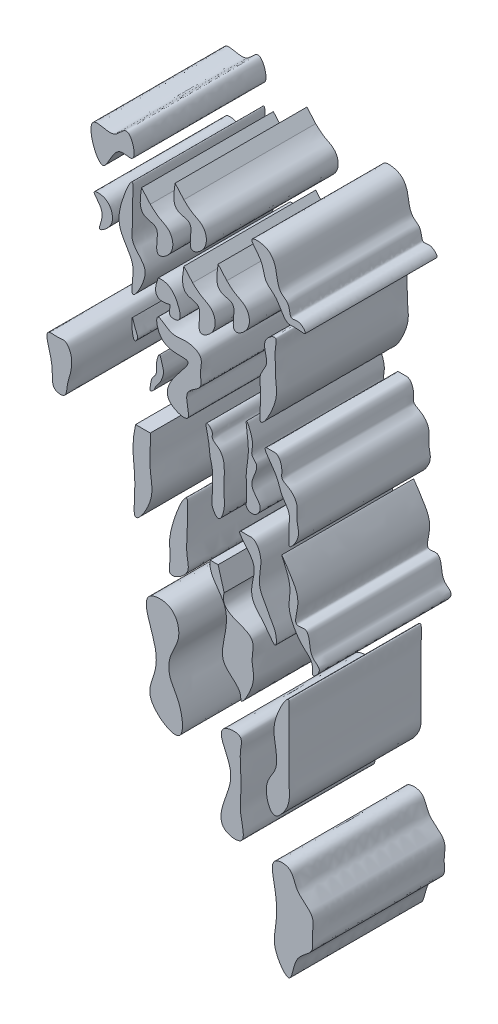
SolidWorks part; units mm, degrees
ref_plane "Front Plane" through (0, 0, 0) normal (0, 0, 1) x (1, 0, 0)
ref_plane "Top Plane" through (0, 0, 0) normal (0, 1, 0) x (1, 0, 0)
ref_plane "Right Plane" through (0, 0, 0) normal (1, 0, 0) x (0, 0, -1)
sketch "Sketch2" plane through (0, 0, 0) normal (0, 0, 1) x (1, 0, 0)
  spline S0 degree 3 poles (-22.2524, -41.5634) (-22.2985, -41.8616) (-22.3666, -42.3025) (-21.7196, -42.3255) (-21.7951, -42.7237) (-21.8014, -43.1952) (-21.2182, -42.8283) (-21.3195, -42.2457) (-21.7452, -42.0964) (-21.9112, -41.9386) (-21.9863, -41.8671) knots 0 0 0 0 0.207427 0.306664 0.423392 0.505521 0.625103 0.799712 0.909285 1 1 1 1
  spline S1 degree 1 poles (-22.2524, -41.5634) (-21.9863, -41.8671) knots 0 0 1 1
  spline S2 degree 3 poles (-19.9285, -42.4109) (-19.9746, -42.7091) (-20.0427, -43.15) (-19.3958, -43.1731) (-19.4713, -43.5712) (-19.4776, -44.0428) (-18.8944, -43.6759) (-18.9956, -43.0932) (-19.4213, -42.9439) (-19.5873, -42.7861) (-19.6625, -42.7146) knots 0 0 0 0 0.207427 0.306664 0.423392 0.505521 0.625103 0.799712 0.909285 1 1 1 1
  spline S3 degree 1 poles (-19.9285, -42.4109) (-19.6625, -42.7146) knots 0 0 1 1
  spline S4 degree 3 poles (-20.9674, -42.985) (-21.0135, -43.2832) (-21.0816, -43.7241) (-20.4347, -43.7472) (-20.5102, -44.1454) (-20.5165, -44.6169) (-19.9333, -44.25) (-20.0345, -43.6674) (-20.4602, -43.518) (-20.6262, -43.3602) (-20.7014, -43.2887) knots 0 0 0 0 0.207427 0.306664 0.423392 0.505521 0.625103 0.799712 0.909285 1 1 1 1
  spline S5 degree 1 poles (-20.9674, -42.985) (-20.7014, -43.2887) knots 0 0 1 1
  spline S6 degree 3 poles (-21.2335, -40.9351) (-21.2796, -41.2333) (-21.3477, -41.6742) (-20.7007, -41.6973) (-20.7762, -42.0954) (-20.7825, -42.567) (-20.1993, -42.2001) (-20.3006, -41.6174) (-20.7263, -41.4681) (-20.8922, -41.3103) (-20.9674, -41.2388) knots 0 0 0 0 0.207427 0.306664 0.423392 0.505521 0.625103 0.799712 0.909285 1 1 1 1
  spline S7 degree 1 poles (-21.2335, -40.9351) (-20.9674, -41.2388) knots 0 0 1 1
  spline S8 degree 3 poles (-23.2714, -42.3458) (-23.8731, -42.3505) (-23.2571, -42.7552) (-23.7014, -43.4714) (-23.1756, -43.0831) (-23.0949, -42.726) (-23.2714, -42.3458) (-23.8731, -42.3505) (-23.2571, -42.7552) knots -0.437374 -0.316138 -0.114431 0 0.189662 0.403883 0.562626 0.683862 0.885569 1 1.189662 1.403883 1.562626 only from (-23.6812, -42.383) to (-23.6812, -42.383)
  spline S9 degree 3 poles (-23.387, -40.5599) (-23.032, -40.6673) (-22.6303, -39.9995) (-22.3217, -41.1038) (-23.1173, -40.7547) (-23.3924, -42.2845) (-24.0158, -40.4835) (-23.387, -40.5599) (-23.032, -40.6673) (-22.6303, -39.9995) knots -0.424588 -0.160212 -0.104486 0 0.110138 0.274978 0.358567 0.575412 0.839788 0.895514 1 1.110138 1.274978 1.358567 only from (-23.0524, -40.5553) to (-23.0524, -40.5553)
  spline S10 degree 3 poles (-22.5598, -42.2755) (-22.4302, -41.158) (-22.9497, -42.3664) (-22.9699, -43.0323) (-22.4602, -43.6249) (-22.5254, -44.0813) (-22.5803, -44.7835) (-22.1406, -44.0125) (-22.1371, -43.4839) (-22.5904, -43.2308) (-22.5129, -42.6878) (-22.5598, -42.2755) (-22.4302, -41.158) (-22.9497, -42.3664) knots -0.24105 -0.196237 -0.113012 0 0.12479 0.252828 0.367116 0.45034 0.495153 0.620686 0.639892 0.75895 0.803763 0.886988 1 1.12479 1.252828 1.367116 only from (-22.5329, -41.5634) to (-22.5329, -41.5634)
  spline S11 degree 3 poles (-21.3311, -45.0368) (-21.8785, -44.491) (-21.7046, -45.5551) (-20.3816, -45.1992) (-21.4324, -46.0924) (-21.5339, -46.8266) (-20.5882, -47.125) (-21.1055, -46.1747) (-20.3669, -45.9979) (-20.5097, -45.5201) (-20.344, -45.0714) (-20.9189, -44.8607) (-21.3311, -45.0368) (-21.8785, -44.491) (-21.7046, -45.5551) knots -0.204826 -0.139309 -0.060255 0 0.079195 0.197262 0.345977 0.419154 0.501786 0.599355 0.681343 0.730128 0.795174 0.860691 0.939745 1 1.079195 1.197262 1.345977 only from (-21.7482, -44.711) to (-21.7482, -44.711)
  spline S12 degree 2 poles (-21.7482, -43.6856) (-22.0062, -44.3801) (-21.391, -44.2015) knots 0 0 0 1 1 1
  spline S13 degree 3 poles (-21.5031, -44.5283) (-21.0997, -44.544) (-21.0716, -44.2973) (-21.17, -43.9986) (-21.3614, -43.6697) (-21.994, -43.6682) (-21.2311, -44.0558) (-21.5031, -44.5283) (-21.0997, -44.544) (-21.0716, -44.2973) knots -0.499676 -0.231732 -0.113108 0 0.067008 0.163276 0.415121 0.500324 0.768268 0.886892 1 1.067008 1.163276 1.415121 only from (-21.1262, -44.4793) to (-21.1262, -44.4793)
  spline S14 degree 3 poles (-18.3873, -41.1949) (-19.1033, -41.1744) (-18.5193, -41.6661) (-18.5663, -42.148) (-18.0752, -42.4207) (-17.9183, -42.9823) (-17.5523, -42.8868) (-17.1653, -42.9863) (-17.4522, -42.6393) (-17.7731, -42.7987) (-17.7388, -42.3751) (-18.1423, -42.1965) (-18.1233, -41.646) (-18.3873, -41.1949) (-19.1033, -41.1744) (-18.5193, -41.6661) knots -0.296451 -0.174734 -0.074505 0 0.090894 0.198006 0.271353 0.397553 0.445449 0.493345 0.547008 0.589582 0.652417 0.703549 0.825266 0.925495 1 1.090894 1.198006 1.271353 only from (-18.8967, -41.2388) to (-18.8967, -41.2388)
  spline S15 degree 3 poles (-18.2274, -43.8795) (-18.1247, -43.3743) (-18.6962, -43.7397) (-18.2963, -44.2516) (-18.6833, -44.6189) (-18.6327, -45.0754) (-18.6345, -45.4055) (-18.7079, -46.233) (-18.0453, -45.0957) (-18.1965, -44.6367) (-18.1776, -44.1468) (-18.2274, -43.8795) (-18.1247, -43.3743) (-18.6962, -43.7397) knots -0.193497 -0.154797 -0.042825 0 0.061538 0.185612 0.277415 0.320071 0.442707 0.506691 0.68135 0.806503 0.845203 0.957175 1 1.061538 1.185612 1.277415 only from (-18.1859, -43.4872) to (-18.1859, -43.4872)
  spline S16 degree 3 poles (-19.8212, -44.9297) (-19.7778, -45.0814) (-19.7075, -45.316) (-19.8699, -45.6331) (-19.7991, -45.8968) (-19.8543, -46.2199) (-19.7216, -46.3873) (-19.7443, -46.5025) knots 0 0 0 0 0.311529 0.40245 0.649147 0.790481 1 1 1 1
  spline S17 degree 2 poles (-19.8212, -44.9297) (-19.6337, -44.8451) (-19.4243, -44.9297) knots 0 0 0 1 1 1
  spline S18 degree 3 poles (-19.6867, -46.3409) (-19.6715, -46.1848) (-19.7137, -45.9788) (-19.6556, -45.6959) (-19.7473, -45.5879) (-19.7558, -45.4397) (-19.5281, -45.4493) (-19.3789, -45.2139) (-19.4356, -45.0294) (-19.4243, -44.9297) knots 0 0 0 0 0.28587 0.413316 0.500189 0.54318 0.656541 0.810786 1 1 1 1
  spline S19 degree 3 poles (-20.0677, -46.892) (-20.3765, -46.6286) (-20.1796, -47.2416) (-20.2055, -47.529) (-20.081, -47.8925) (-20.1185, -48.2182) (-20.0871, -48.5505) (-20.1543, -48.8461) (-19.8862, -49.2484) (-19.7152, -48.7413) (-19.7502, -48.4688) (-19.7413, -48.1815) (-19.7499, -47.8998) (-19.7229, -47.5588) (-19.8397, -47.2415) (-20.1438, -47.1057) (-20.0677, -46.892) (-20.3765, -46.6286) (-20.1796, -47.2416) knots -0.12198 -0.072257 -0.045769 0 0.075531 0.170308 0.22811 0.293872 0.369028 0.425395 0.48449 0.565557 0.621925 0.672029 0.73466 0.794158 0.87802 0.927743 0.954231 1 1.075531 1.170308 1.22811 only from (-20.2625, -46.7614) to (-20.2625, -46.7614)
  spline S20 degree 3 poles (-18.8665, -46.4799) (-19.1345, -45.8737) (-19.0098, -46.6359) (-18.9991, -46.974) (-19.0874, -47.451) (-19.0735, -47.8351) (-19.049, -48.1461) (-19.1027, -48.3847) (-18.8315, -48.523) (-18.4929, -48.1184) (-18.9129, -47.8722) (-18.901, -47.4611) (-18.6379, -47.1349) (-18.9294, -46.9395) (-18.8868, -46.7208) (-18.8665, -46.4799) (-19.1345, -45.8737) (-19.0098, -46.6359) knots -0.169637 -0.137144 -0.085846 0 0.079149 0.188966 0.257139 0.355437 0.416874 0.447592 0.486056 0.555275 0.659524 0.687171 0.796772 0.830363 0.862856 0.914154 1 1.079149 1.188966 1.257139 only from (-19.0672, -46.104) to (-19.0672, -46.104)
  spline S21 degree 3 poles (-18.3193, -46.5099) (-18.6701, -46.4654) (-18.0938, -47.0655) (-18.0576, -47.4948) (-17.7268, -47.8365) (-17.7955, -48.2561) (-17.7625, -48.499) (-17.7943, -48.8616) (-17.396, -48.3553) (-17.5475, -48.0691) (-17.5315, -47.7747) (-17.5173, -47.496) (-17.6899, -47.232) (-18.0228, -47.1162) (-17.9677, -46.8137) (-18.0687, -46.4663) (-18.3193, -46.5099) (-18.6701, -46.4654) (-18.0938, -47.0655) knots -0.14168 -0.052509 -0.02598 0 0.118685 0.212554 0.298047 0.357615 0.441011 0.458882 0.530349 0.619701 0.667356 0.694162 0.779853 0.833126 0.85832 0.947491 0.97402 1 1.118685 1.212554 1.298047 only from (-18.4593, -46.5025) to (-18.4593, -46.5025)
  spline S22 degree 3 poles (-22.5329, -44.9023) (-22.8041, -44.9925) (-22.5598, -45.4033) (-22.8719, -45.6036) (-22.9158, -45.9478) (-22.5257, -45.7617) (-22.5316, -46.4855) (-22.5329, -46.1794) knots 0 0 0 0 0.326883 0.502981 0.618309 0.711705 1 1 1 1
  spline S23 degree 3 poles (-22.5849, -44.7768) (-22.5363, -45.9108) (-22.3424, -45.5443) (-22.4529, -45.3928) (-22.5849, -44.7768) (-22.5363, -45.9108) (-22.3424, -45.5443) knots -0.881147 -0.758565 -0.48528 0 0.118853 0.241435 0.51472 1 1.118853 1.241435 1.51472 only from (-22.4336, -45.684) to (-22.4336, -45.684)
  spline S24 degree 3 poles (-22.5329, -46.1794) (-22.5788, -46.3468) (-22.2742, -46.0467) (-22.4968, -45.8547) (-22.4336, -45.684) knots 0 0 0 0 0.336267 1 1 1 1
  spline S25 degree 1 poles (-22.5329, -44.9297) (-22.5329, -44.9023) knots 0 0 1 1
  spline S26 degree 2 poles (-22.5369, -44.9037) (-22.5312, -45.3254) (-22.5329, -44.9297) knots 0 0 0 1 1 1
  spline S27 degree 3 poles (-21.6371, -45.9018) (-21.6933, -45.5707) (-21.8416, -45.9881) (-21.7496, -46.2155) (-21.9665, -46.4298) (-21.9706, -46.5782) (-22.0184, -46.8049) (-21.8594, -46.7009) (-21.8359, -46.5583) (-21.6982, -46.4344) (-21.624, -46.2596) (-21.5618, -46.0664) (-21.6371, -45.9018) (-21.6933, -45.5707) (-21.8416, -45.9881) knots -0.257132 -0.169808 -0.090825 0 0.092912 0.255546 0.331587 0.430138 0.480228 0.526797 0.585232 0.673735 0.742868 0.830192 0.909175 1 1.092912 1.255546 1.331587 only from (-21.7025, -45.684) to (-21.7025, -45.684)
  spline S28 degree 3 poles (-19.0615, -49.0982) (-19.4794, -49.0438) (-18.6772, -49.7022) (-18.9071, -50.183) (-18.9237, -50.8062) (-18.5713, -51.0432) (-18.1422, -51.738) (-18.1596, -51.1942) (-18.3283, -50.9739) (-18.4703, -50.6492) (-18.7083, -50.3121) (-18.6536, -49.8462) (-18.5957, -49.4332) (-18.8116, -49.0509) (-19.0615, -49.0982) (-19.4794, -49.0438) (-18.6772, -49.7022) knots -0.129915 -0.059333 -0.02998 0 0.115158 0.22682 0.281142 0.413351 0.482986 0.537308 0.591136 0.642048 0.716172 0.797655 0.870085 0.940667 0.97002 1 1.115158 1.22682 1.281142 only from (-19.2412, -49.0882) to (-19.2412, -49.0882)
  spline S29 degree 3 poles (-17.6087, -49.6726) (-18.1451, -48.8417) (-17.6402, -49.7659) (-17.8632, -50.299) (-17.6086, -50.892) (-17.2931, -51.2489) (-17.0184, -51.4467) (-17.1175, -51.9194) (-16.7395, -51.5286) (-17.1191, -51.3377) (-17.1369, -51.0269) (-17.2178, -50.6189) (-17.6562, -50.7858) (-17.4161, -50.0024) (-17.6087, -49.6726) (-18.1451, -48.8417) (-17.6402, -49.7659) knots -0.277133 -0.214526 -0.06399 0 0.099615 0.20491 0.317531 0.378112 0.440135 0.47724 0.525702 0.566148 0.635448 0.682907 0.722867 0.785474 0.93601 1 1.099615 1.20491 1.317531 only from (-17.9945, -49.0882) to (-17.9945, -49.0882)
  spline S30 degree 3 poles (-17.7817, -53.1984) (-17.6859, -52.4328) (-18.3207, -53.576) (-18.1885, -54.1373) (-18.0986, -54.8717) (-18.6127, -55.2898) (-18.3205, -56.2181) (-17.909, -55.8151) (-17.735, -55.4596) (-17.7862, -54.9757) (-17.7721, -54.4938) (-17.7779, -53.9922) (-17.7727, -53.5665) (-17.7817, -53.1984) (-17.6859, -52.4328) (-18.3207, -53.576) knots -0.172413 -0.097259 -0.070734 0 0.117998 0.224098 0.308094 0.405104 0.506158 0.541785 0.615386 0.681699 0.748011 0.827587 0.902741 0.929266 1 1.117998 1.224098 1.308094 only from (-17.7758, -52.798) to (-17.7758, -52.798)
  spline S31 degree 3 poles (-20.1694, -50.3096) (-20.2297, -50.7009) (-19.5697, -51.162) (-19.717, -52.06) (-19.9053, -52.9225) (-19.2312, -53.1813) (-19.2488, -53.7029) (-18.7033, -52.793) (-18.9779, -52.4034) (-18.6861, -51.4278) (-19.9201, -51.555) (-19.7443, -50.958) knots 0 0 0 0 0.161308 0.301606 0.40005 0.52928 0.533968 0.629862 0.737681 0.815345 1 1 1 1
  spline S32 degree 1 poles (-19.9285, -50.3096) (-20.1694, -50.3096) knots 0 0 1 1
  spline S33 degree 1 poles (-19.7443, -50.958) (-19.9285, -50.3096) knots 0 0 1 1
  spline S34 degree 3 poles (-24.7992, -46.7814) (-25.3127, -46.6851) (-24.8428, -47.5345) (-25.0357, -48.214) (-24.519, -48.2464) (-24.5243, -47.8759) (-24.3884, -47.4914) (-24.3162, -47.0672) (-24.5615, -46.7174) (-24.7992, -46.7814) (-25.3127, -46.6851) (-24.8428, -47.5345) knots -0.186681 -0.127243 -0.068516 0 0.229294 0.398764 0.457491 0.551005 0.629583 0.813319 0.872757 0.931484 1 1.229294 1.398764 1.457491 only from (-25.0426, -46.7614) to (-25.0426, -46.7614)
  spline S35 degree 3 poles (-22.4336, -47.8786) (-22.6092, -48.6577) (-22.36, -49.0067) (-22.5568, -50.6781) (-21.816, -49.573) (-22.0518, -48.8301) (-21.9717, -48.1972) (-21.9863, -47.8786) knots 0 0 0 0 0.356746 0.486393 0.643782 0.804777 1 1 1 1
  spline S36 degree 1 poles (-22.4336, -47.8786) (-21.9863, -47.8786) knots 0 0 1 1
  spline S37 degree 3 poles (-21.2542, -52.0428) (-22.4676, -52.0947) (-21.7122, -53.3453) (-21.8423, -54.1688) (-22.1964, -54.9435) (-20.8828, -55.8458) (-21.0357, -54.5176) (-21.435, -54.0508) (-21.4333, -53.3808) (-21.0046, -52.8664) (-21.2542, -52.0428) (-22.4676, -52.0947) (-21.7122, -53.3453) knots -0.263392 -0.166678 -0.077267 0 0.174156 0.268834 0.344543 0.481087 0.595066 0.673723 0.736608 0.833322 0.922733 1 1.174156 1.268834 1.344543 only from (-21.9863, -52.1621) to (-21.9863, -52.1621)
  spline S38 degree 3 poles (-20.8652, -49.4023) (-20.8072, -48.5794) (-21.5332, -50.2565) (-21.3415, -50.7839) (-21.4873, -51.4693) (-20.7538, -51.0483) (-20.9314, -50.4172) (-20.8498, -49.8857) (-20.8652, -49.4023) (-20.8072, -48.5794) (-21.5332, -50.2565) knots -0.323094 -0.120478 -0.068903 0 0.279993 0.416298 0.478925 0.606911 0.676906 0.879522 0.931097 1 1.279993 1.416298 1.478925 only from (-20.8601, -49.0882) to (-20.8601, -49.0882)
  spline S39 degree 3 poles (-19.1539, -54.3905) (-20.1419, -54.4738) (-19.2793, -55.6122) (-19.7917, -56.3111) (-19.9014, -57.2295) (-19.0006, -57.3503) (-19.2912, -56.5594) (-19.229, -56.0074) (-19.2299, -55.3986) (-19.2834, -54.9354) (-19.1539, -54.3905) (-20.1419, -54.4738) (-19.2793, -55.6122) knots -0.216793 -0.121733 -0.078956 0 0.140072 0.332856 0.417853 0.49761 0.604683 0.683394 0.783207 0.878267 0.921044 1 1.140072 1.332856 1.417853 only from (-19.7443, -54.524) to (-19.7443, -54.524)
  spline S40 degree 3 poles (-17.6528, -57.1472) (-18.3934, -57.1535) (-18.1431, -58.0891) (-18.1348, -58.7986) (-18.3057, -59.532) (-17.6735, -60.4302) (-17.6553, -59.3332) (-16.9926, -59.1343) (-17.1046, -58.5939) (-16.9435, -58.0472) (-17.5971, -57.7746) (-17.6528, -57.1472) (-18.3934, -57.1535) (-18.1431, -58.0891) knots -0.234755 -0.133925 -0.060604 0 0.095644 0.254903 0.3451 0.445133 0.542383 0.643214 0.690965 0.765245 0.866075 0.939396 1 1.095644 1.254903 1.3451 only from (-18.1859, -57.2216) to (-18.1859, -57.2216)
  spline S41 degree 3 poles (-17.7758, -57.2216) (-16.8367, -54.6886) (-16.3547, -56.1414) (-16.063, -57.46) (-15.68, -58.2773) (-15.4901, -58.8292) (-14.9408, -59.7822) (-14.5793, -58.9735) (-14.989, -58.6311) (-15.1755, -58.1723) (-15.3466, -57.54) (-15.4923, -56.8676) (-15.4806, -55.845) (-16.076, -55.9) (-16.2912, -55.8818) (-16.462, -55.8866) knots 0 0 0 0 0.244698 0.356543 0.409318 0.496216 0.562412 0.615186 0.652664 0.706898 0.757347 0.838234 0.934168 0.951492 1 1 1 1
extrude "Boss-Extrude1" add sketch "Sketch2" along normal blind 4 contours S34 | S11 | S27 | S23 | S12 S13 | S13 S12 | S10 | S1 S0 | S7 S6 | S8 | S9 | S14 | S3 S2 | S5 S4 | S19 | S20 | S21 | S36 S35 | S38 | S31 S33 S32 | S28 | S29 | S37 | S39 | S30 | S40 | S15 region at (-21.7702, -42.3663, 0) region at (-19.4463, -43.2138, 0) region at (-20.4852, -43.788, 0) region at (-20.7512, -41.738, 0) region at (-23.3717, -42.7621, 0) region at (-23.1941, -40.8746, 0) region at (-22.5679, -43.0635, 0) region at (-20.9203, -46.926, 0) region at (-21.3533, -44.0846, 0) region at (-21.6441, -44.0418, 0) region at (-18.2046, -42.0427, 0) region at (-19.9668, -47.9935, 0) region at (-18.9246, -47.5415, 0) region at (-17.8734, -47.4986, 0) region at (-22.4731, -45.4482, 0) region at (-21.7686, -46.2357, 0) region at (-18.6974, -50.2415, 0) region at (-16.9374, -51.6658, 0) region at (-18.0337, -54.6028, 0) region at (-19.3847, -52.1788, 0) region at (-24.7311, -47.4063, 0) region at (-22.2388, -48.9935, 0) region at (-21.5611, -53.7215, 0) region at (-21.1047, -50.3066, 0) region at (-19.4786, -55.9082, 0) region at (-17.7292, -58.5561, 0)
